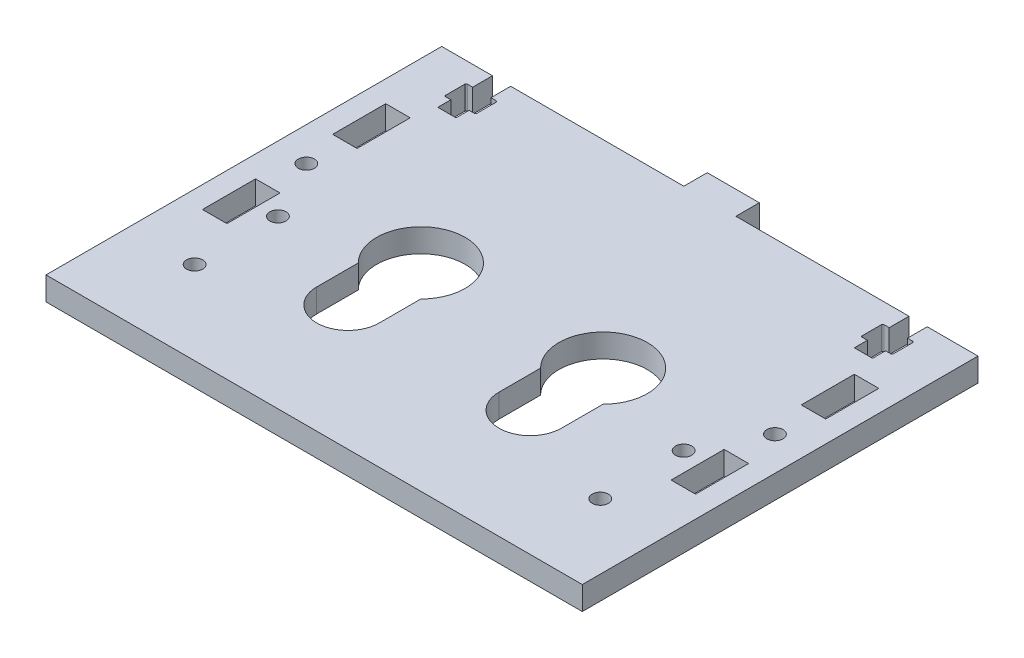
SolidWorks part; units mm, degrees
ref_plane "Front Plane" through (0, 0, 0) normal (0, 0, 1) x (1, 0, 0)
ref_plane "Top Plane" through (0, 0, 0) normal (0, 1, 0) x (1, 0, 0)
ref_plane "Right Plane" through (0, 0, 0) normal (1, 0, 0) x (0, 0, -1)
sketch "Sketch1" plane through (0, 0, 0) normal (0, 1, 0) x (1, 0, 0)
  line L1 (-51.5, 38) -> (51.5, 38)
  line L2 (-51.5, 38) -> (-51.5, -38)
  line L3 (-51.5, -38) -> (51.5, -38)
  line L4 (51.5, 38) -> (51.5, -38)
  line L5 (-51.5, 38) -> (51.5, -38) construction
  line L6 (-51.5, -38) -> (51.5, 38) construction
  point P0 (0, 0)
  dimension "D1" = 103
  dimension "D2" = 76
extrude "MainShape" add sketch "Sketch1" along normal blind 4.5
sketch "Sketch2" plane through (0, 4.5, 0) normal (0, 1, 0) x (1, 0, 0)
  line L0 (0, -38) -> (0, 38) construction
  line L1 (-51.5, -38) -> (51.5, -38) construction
  line L2 (51.5, 38) -> (-51.5, 38) construction
  line L4 (-5, 42.5) -> (5, 42.5)
  line L5 (-5, 42.5) -> (-5, 33.5)
  line L6 (-5, 33.5) -> (5, 33.5)
  line L7 (5, 42.5) -> (5, 33.5)
  line L8 (-5, 42.5) -> (5, 33.5) construction
  line L9 (-5, 33.5) -> (5, 42.5) construction
  dimension "D1" = 10
  dimension "D2" = 4.5
extrude "Tab1" add sketch "Sketch2" against normal through all
sketch "Sketch4" plane through (0, 4.5, 0) normal (0, 1, 0) x (1, 0, 0)
  line L0 (0, 42.5) -> (0, -38) construction
  line L1 (5, 42.5) -> (-5, 42.5) construction
  line L2 (-51.5, -38) -> (51.5, -38) construction
  line L3 (-40, 38) -> (-40, 27.5) construction
  line L4 (-5, 38) -> (-51.5, 38) construction
  line L5 (-38.25, 27.5) -> (-41.75, 27.5) construction
  line L6 (-41.75, 27.5) -> (-41.75, 38) construction
  line L7 (-38.25, 27.5) -> (-41.75, 27.5)
  line L8 (-41.75, 27.5) -> (-41.75, 30)
  line L9 (-41.75, 30) -> (-42.75, 30)
  line L10 (-43, 30.25) -> (-43, 33.95)
  line L11 (-42.75, 34.2) -> (-41.75, 34.2)
  line L12 (-41.75, 34.2) -> (-41.75, 38)
  line L13 (-41.75, 38) -> (-38.25, 38)
  line L14 (-38.25, 27.5) -> (-38.25, 38) construction
  line L15 (-38.25, 34.2) -> (-38.25, 38)
  line L16 (-37.25, 34.2) -> (-38.25, 34.2)
  line L17 (-37, 30.25) -> (-37, 33.95)
  line L18 (-38.25, 30) -> (-37.25, 30)
  line L19 (-38.25, 27.5) -> (-38.25, 30)
  line L20 (38.25, 27.5) -> (38.25, 38) construction
  line L21 (41.75, 27.5) -> (41.75, 38) construction
  line L22 (38.25, 27.5) -> (41.75, 27.5) construction
  line L23 (40, 38) -> (40, 27.5) construction
  line L24 (38.25, 27.5) -> (38.25, 30)
  line L25 (38.25, 30) -> (37.25, 30)
  line L26 (37, 30.25) -> (37, 33.95)
  line L27 (37.25, 34.2) -> (38.25, 34.2)
  line L28 (38.25, 34.2) -> (38.25, 38)
  line L29 (41.75, 38) -> (38.25, 38)
  line L30 (41.75, 34.2) -> (41.75, 38)
  line L31 (42.75, 34.2) -> (41.75, 34.2)
  line L32 (43, 30.25) -> (43, 33.95)
  line L33 (41.75, 30) -> (42.75, 30)
  line L34 (41.75, 27.5) -> (41.75, 30)
  line L35 (38.25, 27.5) -> (41.75, 27.5)
  arc A0 (-42.75, 30) -> (-43, 30.25) centre (-42.75, 30.25) cw
  arc A1 (-37, 30.25) -> (-37.25, 30) centre (-37.25, 30.25) cw
  arc A2 (-37.25, 34.2) -> (-37, 33.95) centre (-37.25, 33.95) cw
  arc A3 (-43, 33.95) -> (-42.75, 34.2) centre (-42.75, 33.95) cw
  arc A4 (43, 33.95) -> (42.75, 34.2) centre (42.75, 33.95) ccw
  arc A5 (37.25, 34.2) -> (37, 33.95) centre (37.25, 33.95) ccw
  arc A6 (37, 30.25) -> (37.25, 30) centre (37.25, 30.25) ccw
  arc A7 (42.75, 30) -> (43, 30.25) centre (42.75, 30.25) ccw
  point P24 (-43, 30)
  point P27 (-37, 30)
  point P30 (-37, 34.2)
  point P33 (-43, 34.2)
  point P56 (43, 34.2)
  point P57 (37, 34.2)
  point P58 (37, 30)
  point P59 (43, 30)
  dimension "D7" = 0.25
  dimension "D1" = 10.5
  dimension "D2" = 1.75
  dimension "D3" = 4.2
  dimension "D4" = 3
  dimension "D5" = 8
  dimension "D6" = 40
extrude "Cut-Extrude2" cut sketch "Sketch4" against normal through all
sketch "Sketch5" plane through (0, 4.5, 0) normal (0, 1, 0) x (1, 0, 0)
  line L0 (0, -38) -> (0, 42.5) construction
  line L1 (-51.5, -38) -> (51.5, -38) construction
  line L2 (5, 42.5) -> (-5, 42.5) construction
  line L3 (45, 38) -> (45, -38) construction
  line L4 (51.5, 38) -> (41.75, 38) construction
  line L5 (-45, 38) -> (-45, -38) construction
  line L6 (42.65, 23.1) -> (47.35, 23.1)
  line L7 (42.65, 23.1) -> (42.65, 12.9)
  line L8 (42.65, 12.9) -> (47.35, 12.9)
  line L9 (47.35, 23.1) -> (47.35, 12.9)
  line L10 (42.65, 23.1) -> (47.35, 12.9) construction
  line L11 (42.65, 12.9) -> (47.35, 23.1) construction
  line L12 (-42.65, 12.9) -> (-47.35, 23.1) construction
  line L13 (-42.65, 23.1) -> (-47.35, 12.9) construction
  line L14 (-47.35, 23.1) -> (-47.35, 12.9)
  line L15 (-42.65, 12.9) -> (-47.35, 12.9)
  line L16 (-42.65, 23.1) -> (-42.65, 12.9)
  line L17 (-42.65, 23.1) -> (-47.35, 23.1)
  line L18 (-51.5, 5.5) -> (51.5, 5.5) construction
  line L19 (-51.5, 38) -> (-51.5, -38) construction
  line L20 (51.5, -38) -> (51.5, 38) construction
  line L21 (-42.65, -12.1) -> (-47.35, -1.9) construction
  line L22 (-42.65, -1.9) -> (-47.35, -12.1) construction
  line L23 (42.65, -1.9) -> (47.35, -12.1) construction
  line L24 (42.65, -12.1) -> (47.35, -1.9) construction
  line L25 (-42.65, -12.1) -> (-47.35, -12.1)
  line L26 (-42.65, -12.1) -> (-42.65, -1.9)
  line L27 (-42.65, -1.9) -> (-47.35, -1.9)
  line L28 (-47.35, -12.1) -> (-47.35, -1.9)
  line L29 (47.35, -12.1) -> (47.35, -1.9)
  line L30 (42.65, -1.9) -> (47.35, -1.9)
  line L31 (42.65, -12.1) -> (42.65, -1.9)
  line L32 (42.65, -12.1) -> (47.35, -12.1)
  line L33 (-42.65, 23.1) -> (-47.35, 12.9) construction
  circle A0 centre (45, 5.5) radius 1.55
  circle A1 centre (-45, 5.5) radius 1.55
  point P10 (45, 18)
  point P21 (-45, 18)
  point P36 (-45, -7)
  point P37 (45, -7)
  dimension "D6" = 3.1
  dimension "D1" = 45
  dimension "D2" = 10.2
  dimension "D3" = 4.7
  dimension "D4" = 20
  dimension "D5" = 25
extrude "Cut-Extrude3" cut sketch "Sketch5" against normal through all
sketch "Sketch6" plane through (0, 4.5, 0) normal (0, 1, 0) x (1, 0, 0)
  line L0 (-17.5, -38) -> (-17.5, 28) construction
  line L1 (-23.5, -14) -> (-23.5, -6.0208)
  line L2 (5, 42.5) -> (-5, 42.5) construction
  line L3 (-51.5, -14) -> (51.5, -14) construction
  line L4 (-51.5, 38) -> (-51.5, -38) construction
  line L5 (51.5, -38) -> (51.5, 38) construction
  line L6 (51.5, 38) -> (41.75, 38) construction
  line L7 (-51.5, -38) -> (51.5, -38) construction
  line L8 (-11.5, -14) -> (-11.5, -6.0208)
  line L9 (-51.5, 38) -> (51.5, 38) construction
  arc A0 (-23.5, -14) -> (-11.5, -14) centre (-17.5, -14) ccw
  arc A2 (-11.5, -6.0208) -> (-23.5, -6.0208) centre (-17.5, 0) ccw
  point P4 (0, 42.5)
  dimension "D1" = 12
  dimension "D6" = 8.5
  dimension "D2" = 52
  dimension "D3" = 0
  dimension "D4" = 17.5
  dimension "D5" = 0
  dimension "D7" = 14
extrude "Cut-Extrude4" cut sketch "Sketch6" against normal through all
sketch "Sketch8" plane through (0, 4.5, 0) normal (0, 1, 0) x (1, 0, 0)
  line L0 (-17.5, -8) -> (-17.5, -20) construction
  line L1 (-17.5, -14) -> (-38.96, -14) construction
  line L2 (-38.96, -22) -> (-38.96, -6) construction
  line L3 (-17.5, -20) -> (-17.5, -8) construction
  circle A0 centre (-38.96, -6) radius 1.55
  circle A1 centre (-17.5, -14) radius 6 construction
  circle A2 centre (-38.96, -22) radius 1.55
  dimension "D3" = 3.1
  dimension "D1" = 0
  dimension "D2" = 8
  dimension "D4" = 21.46
extrude "Cut-Extrude6" cut sketch "Sketch8" against normal through all
sketch "Sketch9" plane through (0, 4.5, 0) normal (0, 1, 0) x (1, 0, 0)
  line L0 (0, -38) -> (0, 42.5) construction
  line L1 (-51.5, -38) -> (51.5, -38) construction
  line L2 (5, 42.5) -> (-5, 42.5) construction
  line L3 (20, -38) -> (20, -27.5) construction
  line L4 (18.25, -27.5) -> (21.75, -27.5) construction
  line L5 (21.75, -27.5) -> (21.75, -38) construction
  line L6 (21.75, -38) -> (21.75, -34.2)
  line L7 (21.75, -34.2) -> (22.75, -34.2)
  line L8 (23, -33.95) -> (23, -30.25)
  line L9 (22.75, -30) -> (21.75, -30)
  line L10 (21.75, -30) -> (21.75, -27.5)
  line L11 (21.75, -27.5) -> (18.25, -27.5)
  line L12 (21.75, -38) -> (18.25, -38)
  line L13 (18.25, -27.5) -> (18.25, -38) construction
  line L14 (18.25, -30) -> (18.25, -27.5)
  line L15 (17.25, -30) -> (18.25, -30)
  line L16 (17, -33.95) -> (17, -30.25)
  line L17 (18.25, -34.2) -> (17.25, -34.2)
  line L18 (18.25, -38) -> (18.25, -34.2)
  line L19 (-18.25, -27.5) -> (-18.25, -38) construction
  line L20 (-21.75, -27.5) -> (-21.75, -38) construction
  line L21 (-18.25, -27.5) -> (-21.75, -27.5) construction
  line L22 (-20, -38) -> (-20, -27.5) construction
  line L23 (-18.25, -38) -> (-18.25, -34.2)
  line L24 (-18.25, -34.2) -> (-17.25, -34.2)
  line L25 (-17, -33.95) -> (-17, -30.25)
  line L26 (-17.25, -30) -> (-18.25, -30)
  line L27 (-18.25, -30) -> (-18.25, -27.5)
  line L28 (-21.75, -38) -> (-18.25, -38)
  line L29 (-21.75, -27.5) -> (-18.25, -27.5)
  line L30 (-21.75, -30) -> (-21.75, -27.5)
  line L31 (-22.75, -30) -> (-21.75, -30)
  line L32 (-23, -33.95) -> (-23, -30.25)
  line L33 (-21.75, -34.2) -> (-22.75, -34.2)
  line L34 (-21.75, -38) -> (-21.75, -34.2)
  arc A0 (22.75, -34.2) -> (23, -33.95) centre (22.75, -33.95) ccw
  arc A1 (23, -30.25) -> (22.75, -30) centre (22.75, -30.25) ccw
  arc A2 (17, -30.25) -> (17.25, -30) centre (17.25, -30.25) cw
  arc A3 (17.25, -34.2) -> (17, -33.95) centre (17.25, -33.95) cw
  arc A4 (-17.25, -34.2) -> (-17, -33.95) centre (-17.25, -33.95) ccw
  arc A5 (-17, -30.25) -> (-17.25, -30) centre (-17.25, -30.25) ccw
  arc A6 (-23, -30.25) -> (-22.75, -30) centre (-22.75, -30.25) cw
  arc A7 (-22.75, -34.2) -> (-23, -33.95) centre (-22.75, -33.95) cw
  point P16 (23, -34.2)
  point P19 (23, -30)
  point P30 (17, -30)
  point P31 (17, -34.2)
  point P54 (-17, -34.2)
  point P55 (-17, -30)
  point P56 (-23, -30)
  point P57 (-23, -34.2)
  dimension "D7" = 0.25
  dimension "D1" = 10.5
  dimension "D2" = 1.75
  dimension "D3" = 8
  dimension "D4" = 4.2
  dimension "D5" = 3
  dimension "D6" = 20
extrude "Cut-Extrude7" [suppressed] cut sketch "Sketch9" against normal through all
sketch "Sketch10" [suppressed] plane through (0, 0, 28) normal (0, 0, 1) x (1, 0, 0)
  line L0 (-55, 2.25) -> (55, 2.25) construction
  line L1 (-55, 4.5) -> (-55, 0) construction
  line L2 (55, 4.5) -> (55, 0) construction
  line L3 (-16, 4.5) -> (-16, 0) construction
  line L4 (-14.25, 4.5) -> (-17.75, 4.5) construction
  line L5 (16, 4.5) -> (16, 0) construction
  line L6 (17.75, 4.5) -> (14.25, 4.5) construction
  line L7 (17.75, 0) -> (14.25, 0) construction
  line L8 (-14.25, 0) -> (-17.75, 0) construction
  circle A0 centre (-16, 2.25) radius 1.6
  circle A1 centre (16, 2.25) radius 1.6
  dimension "D1" = 3.2
  dimension "D2" = 3.2
mirror "Mirror1" about plane through (0, 0, 0) normal (1, 0, 0) of "Cut-Extrude6", "Cut-Extrude4"
equation "\"X-ROD-SPACING\"=45"
equation "\"Y-ROD-SPACING\"=75"
equation "\"Z-ROD-SPACING\"=17.5"
equation "\"Y-BED-OFFSET\"=2"
equation "\"Y-BED-ROD-INSET\"=3.5"
equation "\"Y-BED-SCREW-SPACING\"=209"
equation "\"Y-BED-SCREW-CUTOUT-SLOT-HEIGHT\"=2"
equation "\"T-SLOT-NUT-FILLET-RADIUS\"=0.25"
equation "\"T-SLOT-SCREW-SHAFT-RADIUS\"=1.75"
equation "\"T-SLOT-SCREW-SHAFT-CUTOUT-LENGTH\"=10.5"
equation "\"T-SLOT-NUT-DEPTH\"=4.2"
equation "\"T-SLOT-NUT-WIDTH\"=3"
equation "\"T-SLOT-NUT-END-DISTANCE\"=8"
equation "\"ACRYLIC-THICKNESS\"=10"
equation "\"ACRYLIC-THICKNESS2\"=4.5"
equation "\"ACRYLIC-TAB-CUTOUT-SIZE\"=\"ACRYLIC-THICKNESS\"+\"ACRYLIC-TAB-TOLERANCE\"*2"
equation "\"ACRYLIC-TAB-WIDTH\"=\"ACRYLIC-THICKNESS\""
equation "\"ACRYLIC-M3-HOLE\"=3.1"
equation "\"SMOOTHROD-CAP-SCREW-DISTANCE\"=20"
equation "\"FRAME-WIDTH-INNER\"=370"
equation "\"NEMA17-HOLE-SPACING\"=31"
equation "\"NEMA17-CENTRAL-CUTOUT\"=22.5"
equation "\"Z-BRACKET-REACH\"=55"
equation "\"Z-ROD-INSET\"=16"
equation "\"TOP-BRACKET-SPACING\"=40"
equation "\"SMOOTHROD-X-LENGTH\"=350"
equation "\"SMOOTHROD-Y-LENGTH\"=350"
equation "\"SMOOTHROD-Z-LENGTH\"=350"
equation "\"SMOOTHROD-TIGHTENING-HEADROOM\"=.25"
equation "\"LEADSCREW-Z-LENGTH\"=300"
equation "\"SCREW-LENGTH-FRAME\"=\"ACRYLIC-THICKNESS\" + 10"
equation "\"SCREW-LENGTH-MOTOR\"=\"ACRYLIC-THICKNESS\" + 5"
equation "\"SCREW-LENGTH-EXTRUDER\"=28"
equation "\"SCREW-HEAD-RADIUS\"=6"
equation "\"PRINTED-X-SMOOTHROD-DIAMETER\"=8.2"
equation "\"PRINTED-X-SMOOTHROD-CUTOUT\"=10"
equation "\"PRINTED-X-BASE-HEIGHT\"=10"
equation "\"PRINTED-LM8UU-CUTOUT-SIZE\"=15.25"
equation "\"PRINTED-LM8UU-CUTOUT-LENGTH\"=24.5"
equation "\"PRINTED-X-IDLER-HEIGHT\"=16"
equation "\"PSU-MOUNTING-WIDTH\"=95"
equation "\"PSU-MOUNTING-HEIGHT\"=177"
equation "\"Y-BELT-TO-ROD-DISTANCE\"=20"
equation "\"SPOOL-HOLDER-ROD-SPACING\"=150"
equation "\"ACRYLIC-X-CARRIAGE-WIDTH\"=55"
equation "\"ACRYLIC-X-CARRIAGE-HEIGHT\"=75"
equation "\"ACRYLIC-X-CARRIAGE-SCREW-SPACING-X\"=15"
equation "\"ACRYLIC-X-CARRIAGE-SCREW-SPACING-Y\"=33"
equation "\"ACRYLIC-X-CARRIAGE-CENTER-TAB-SPACING\"=14"
equation "\"D1@MainShape\" = \"ACRYLIC-THICKNESS2\""
equation "\"D1@Sketch2\"=\"ACRYLIC-TAB-WIDTH\""
equation "\"D2@Sketch2\"=\"ACRYLIC-THICKNESS2\""
equation "\"D1@Sketch4\"=\"T-SLOT-SCREW-SHAFT-CUTOUT-LENGTH\""
equation "\"D2@Sketch4\"=\"T-SLOT-SCREW-SHAFT-RADIUS\""
equation "\"D3@Sketch4\"=\"T-SLOT-NUT-DEPTH\""
equation "\"D4@Sketch4\"=\"T-SLOT-NUT-WIDTH\""
equation "\"D5@Sketch4\"=\"T-SLOT-NUT-END-DISTANCE\""
equation "\"D7@Sketch4\"=\"T-SLOT-NUT-FILLET-RADIUS\""
equation "\"ACRYLIC-X-CARRIAGE-EXTRUDER-SHELF-DEPTH\"=\"ACRYLIC-X-CARRIAGE-EXTRUDER-OFFSET\" + 28"
equation "\"ACRYLIC-X-CARRIAGE-LM8UU-CUTOUT-WIDTH\"=24.25"
equation "\"ACRYLIC-X-CARRIAGE-EXTRUDER-BRACE-SPACING\"=23"
equation "\"ACRYLIC-X-CARRIAGE-EXTRUDER-BRACE-TAB-OFFSET\"=20"
equation "\"ACRYLIC-X-CARRIAGE-EXTRUDER-BRACE-HEIGHT\"=35"
equation "\"ACRYLIC-X-CARRIAGE-EXTRUDER-BRACE-SCREW-SPACING\"=22"
equation "\"D2@Sketch5\"=\"ACRYLIC-TAB-CUTOUT-SIZE\""
equation "\"D3@Sketch5\"=\"ACRYLIC-THICKNESS2\"+\"ACRYLIC-TAB-TOLERANCE\"*2"
equation "\"D4@Sketch5\"=\"ACRYLIC-X-CARRIAGE-EXTRUDER-BRACE-TAB-OFFSET\""
equation "\"D3@Sketch8\"=\"ACRYLIC-M3-HOLE\""
equation "\"ACRYLIC-X-CARRIAGE-EXTRUDER-ANGLE\"=90"
equation "\"ACRYLIC-X-CARRIAGE-EXTRUDER-OFFSET\"=26"
equation "\"D6@Sketch5\"=\"ACRYLIC-M3-HOLE\""
equation "\"D1@Sketch9\"=\"T-SLOT-SCREW-SHAFT-CUTOUT-LENGTH\""
equation "\"D2@Sketch9\"=\"T-SLOT-SCREW-SHAFT-RADIUS\""
equation "\"D3@Sketch9\"=\"T-SLOT-NUT-END-DISTANCE\""
equation "\"D4@Sketch9\"=\"T-SLOT-NUT-DEPTH\""
equation "\"D5@Sketch9\"=\"T-SLOT-NUT-WIDTH\""
equation "\"D7@Sketch9\"=\"T-SLOT-NUT-FILLET-RADIUS\""
equation "\"ACRYLIC-TAB-TOLERANCE\"=.1"
equation "\"ACRYLIC-X-CARRIAGE-DUAL-WIDTH-MULTIPLIER\"=1.65"
equation "\"ACRYLIC-X-CARRIAGE-DUAL-HOTEND-SPACING\"=42"
equation "\"ACRYLIC-X-CARRIAGE-DUAL-WIDTH\"=103"
equation "\"ACRYLIC-X-CARRIAGE-DUAL-HOTEND-SEPARATION\"=35"
equation "\"ACRYLIC-X-CARRIAGE-DUAL-MOUNT-PLATE-DEPTH\"=76"
equation "\"ACRYLIC-X-CARRIAGE-DUAL-MOUNT-BRACE-WIDTH\"=45"
equation "\"D1@Sketch5\"=\"ACRYLIC-X-CARRIAGE-DUAL-MOUNT-BRACE-WIDTH\""
equation "\"ACRYLIC-X-CARRIAGE-DUAL-MOUNT-SCREW-WIDTH\"=40"
equation "\"D6@Sketch4\"=\"ACRYLIC-X-CARRIAGE-DUAL-MOUNT-SCREW-WIDTH\""
equation "\"D1@Sketch1\"=\"ACRYLIC-X-CARRIAGE-DUAL-WIDTH\""
equation "\"D2@Sketch1\"=\"ACRYLIC-X-CARRIAGE-DUAL-MOUNT-PLATE-DEPTH\""
equation "\"D4@Sketch6\"=\"ACRYLIC-X-CARRIAGE-DUAL-HOTEND-SEPARATION\"/2"
